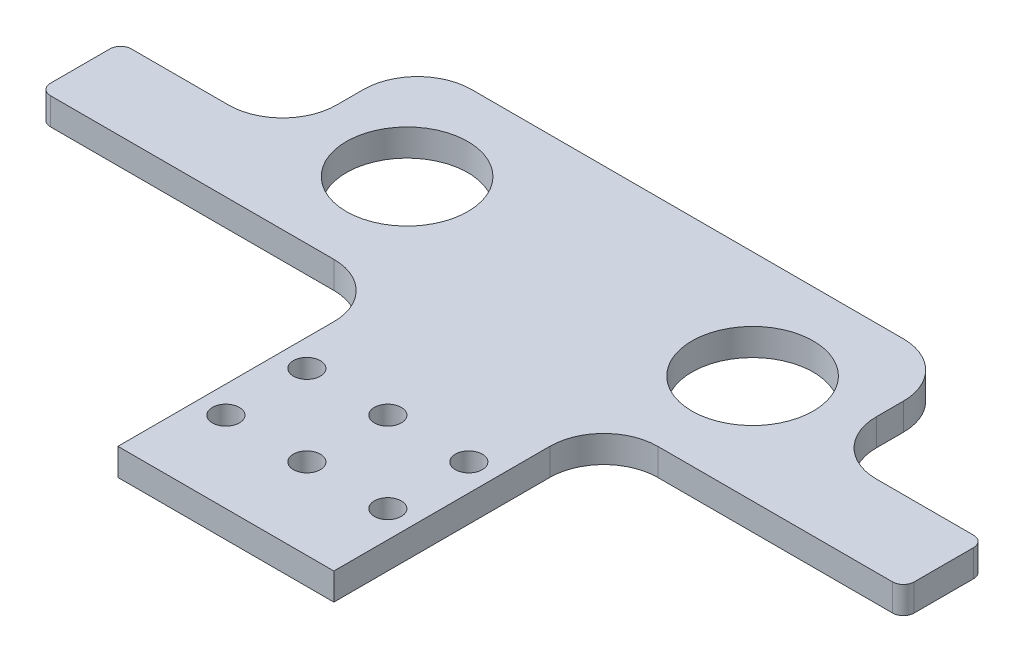
SolidWorks part; units mm, degrees
ref_plane "Front Plane" through (0, 0, 0) normal (0, 0, 1) x (1, 0, 0)
ref_plane "Top Plane" through (0, 0, 0) normal (0, 1, 0) x (1, 0, 0)
ref_plane "Right Plane" through (0, 0, 0) normal (1, 0, 0) x (0, 0, -1)
sketch "Sketch2" plane through (0, 0, 0) normal (0, 1, 0) x (1, 0, 0)
  line L1 (-52.4007, -9.869) -> (74.5993, -9.869)
  line L2 (-52.4007, -9.869) -> (-52.4007, 40.931)
  line L3 (-52.4007, 40.931) -> (74.5993, 40.931)
  line L4 (74.5993, -9.869) -> (74.5993, 40.931)
  line L5 (-52.4007, -9.869) -> (74.5993, 40.931) construction
  line L6 (-52.4007, 40.931) -> (74.5993, -9.869) construction
  point P0 (11.0993, 15.531)
  dimension "D1" = 127
  dimension "D2" = 50.8
extrude "Boss-Extrude1" add sketch "Sketch2" along normal blind 6.35
ref_plane "Plane1" through (11.0993, 0, 0) normal (1, 0, 0) x (0, 0, -1)
sketch "Sketch3" plane through (0, 6.35, 0) normal (0, 1, 0) x (1, 0, 0)
  line L0 (11.0993, -3.4925) -> (11.0993, 3.4925) construction
  line L2 (74.5993, 40.931) -> (-52.4007, 40.931) construction
  circle A0 centre (-29.5407, 15.6148) radius 14.2875
  dimension "D1" = 28.575
  dimension "D2" = 40.64
  dimension "D3" = 25.3163
extrude "Cut-Extrude1" cut sketch "Sketch3" against normal blind 6.35 contours A0
mirror "Mirror1" about plane through (11.0993, 0, 0) normal (1, 0, 0) of "Cut-Extrude1"
sketch "Sketch6" plane through (0, 6.35, 0) normal (0, 1, 0) x (1, 0, 0)
  line L0 (-52.4007, 40.931) -> (-52.4007, -9.869) construction
  line L1 (-90.5007, 9.181) -> (-52.4007, 9.181)
  line L2 (-90.5007, 9.181) -> (-90.5007, -9.869)
  line L3 (-90.5007, -9.869) -> (-52.4007, -9.869)
  line L4 (-52.4007, 9.181) -> (-52.4007, -9.869)
  line L5 (-52.4007, -9.869) -> (74.5993, -9.869) construction
  dimension "D1" = 38.1
  dimension "D2" = 0
  dimension "D3" = 0
  dimension "D4" = 19.05
extrude "Boss-Extrude2" add sketch "Sketch6" against normal blind 6.35
mirror "Mirror2" about plane through (11.0993, 0, 0) normal (1, 0, 0) of "Boss-Extrude2"
fillet "Fillet2" radius 12.7 4 edges at (74.5993, 3.175, -9.181) (-52.4007, 3.175, -9.181) (-52.4007, 3.175, -40.931) (74.5993, 3.175, -40.931)
fillet "Fillet1" radius 2.54 4 edges at (112.6993, 3.175, 9.869) (112.6993, 3.175, -9.181) (-90.5007, 3.175, 9.869) (-90.5007, 3.175, -9.181)
sketch "Sketch8" plane through (0, 6.35, 0) normal (0, 1, 0) x (1, 0, 0)
  line L0 (-87.9607, -9.869) -> (110.1593, -9.869) construction
  line L1 (-8.5857, -9.869) -> (42.2143, -9.869)
  line L2 (-8.5857, -9.869) -> (-8.5857, -73.369)
  line L3 (-8.5857, -73.369) -> (42.2143, -73.369)
  line L4 (42.2143, -9.869) -> (42.2143, -73.369)
  line L5 (112.6993, 6.641) -> (112.6993, -7.329) construction
  dimension "D1" = 50.8
  dimension "D2" = 63.5
  dimension "D3" = 70.485
extrude "Boss-Extrude3" add sketch "Sketch8" against normal blind 6.35 contours L3 L4 L1 L2
fillet "Fillet3" radius 12.7 2 edges at (42.2143, 3.175, 9.869) (-8.5857, 3.175, 9.869)
sketch "Sketch9" plane through (0, 6.35, 0) normal (0, 1, 0) x (1, 0, 0)
  line L0 (-8.5857, -22.569) -> (-8.5857, -73.369) construction
  line L1 (-8.5857, -73.369) -> (42.2143, -73.369) construction
  circle A0 centre (-2.2357, -54.319) radius 3.175
  dimension "D1" = 6.35
  dimension "D2" = 6.35
  dimension "D3" = 19.05
extrude "Cut-Extrude2" cut sketch "Sketch9" against normal blind 6.35
pattern_linear "LPattern1" count 3 spacing 19.05 along (1, 0, 0) count 2 spacing 19.05 along (0, 0, -1) of "Cut-Extrude2"
